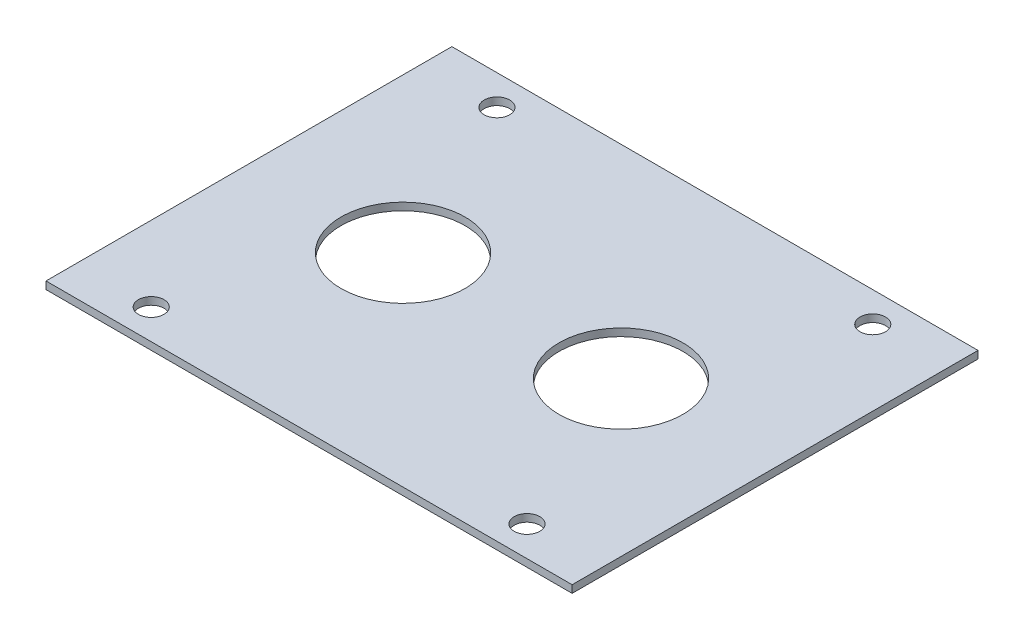
SolidWorks part; units mm, degrees
ref_plane "Plan de face" through (0, 0, 0) normal (0, 0, 1) x (1, 0, 0)
ref_plane "Plan de dessus" through (0, 0, 0) normal (0, 1, 0) x (1, 0, 0)
ref_plane "Plan de droite" through (0, 0, 0) normal (1, 0, 0) x (0, 0, -1)
sketch "Esquisse1" plane through (0, 0, 0) normal (0, 1, 0) x (1, 0, 0)
  line L1 (-35, 27) -> (35, 27)
  line L2 (-35, 27) -> (-35, -27)
  line L3 (-35, -27) -> (35, -27)
  line L4 (35, 27) -> (35, -27)
  line L5 (-35, 27) -> (35, -27) construction
  line L6 (-35, -27) -> (35, 27) construction
  point P0 (0, 0)
  dimension "D1" = 54
  dimension "D2" = 70
extrude "Boss.-Extru.1" add sketch "Esquisse1" along normal blind 1
sketch "Esquisse2" plane through (0, 1, 0) normal (0, 1, 0) x (1, 0, 0)
  line L0 (-35, -27) -> (35, -27) construction
  line L1 (-35, 27) -> (-35, -27) construction
  circle A0 centre (-14.5, 0) radius 8.25
  dimension "D1" = 16.5
  dimension "D2" = 27
  dimension "D3" = 20.5
extrude "Enlèv. mat.-Extru.1" cut sketch "Esquisse2" against normal blind 10
sketch "Esquisse4" plane through (0, 1, 0) normal (0, 1, 0) x (1, 0, 0)
  line L0 (35, -27) -> (35, 27) construction
  line L1 (-35, -27) -> (35, -27) construction
  circle A0 centre (14.5, 0) radius 8.25
  dimension "D1" = 16.5
  dimension "D2" = 20.5
  dimension "D3" = 27
extrude "Enlèv. mat.-Extru.3" cut sketch "Esquisse4" against normal blind 10
sketch "Sketch3" plane through (0, 1, 0) normal (0, 1, 0) x (1, 0, 0)
  line L0 (-35, 27) -> (-35, -27) construction
  line L1 (-35, -27) -> (35, -27) construction
  point P0 (-25, -23)
  point P12 (25, -23)
  point P13 (25, 23)
  point P14 (-25, 23)
  dimension "D1" = 10
  dimension "D2" = 4
  dimension "D3" = 2
  dimension "D4" = 2
hole_wizard "M3 Clearance Hole1" positions "Sketch3" profile "Sketch2" hole size "M3" standard "ISO" end condition through all
sketch "Sketch2" plane through (-25, 1, 23) normal (1, 0, 0) x (0, 0, 1)
  line L0 (0, 0) -> (0, 1)
  line L1 (0, 1) -> (1.7, 1)
  line L2 (1.7, 1) -> (1.7, 0)
  line L5 (1.7, 0) -> (0, 0)
  line L11 (0, -6.35) -> (0, 107.95) construction
  dimension "Thru Hole Dia." = 3.4
  dimension "Thru Hole Depth" = 1
